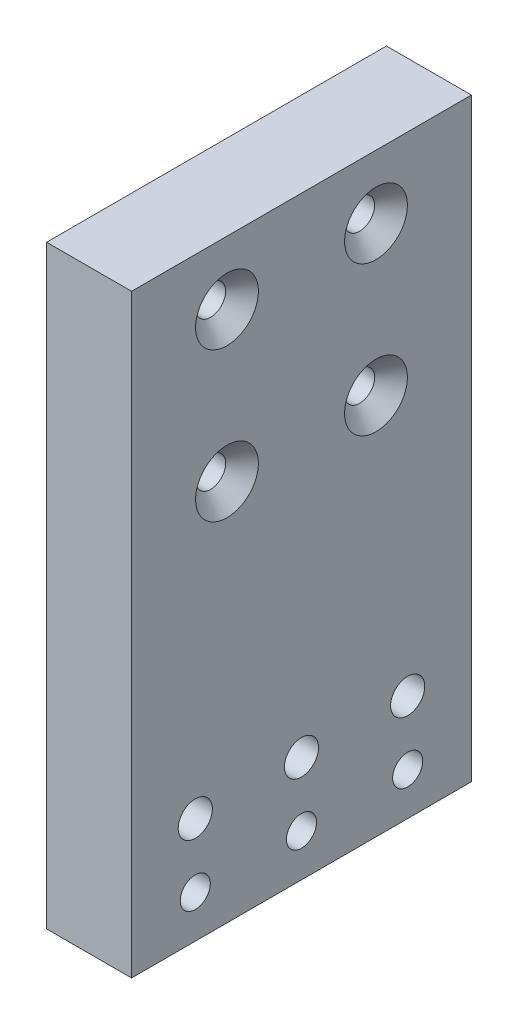
SolidWorks part; units mm, degrees
material "Nylon 6/10"
ref_plane "Front Plane" through (0, 0, 0) normal (0, 0, 1) x (1, 0, 0)
ref_plane "Top Plane" through (0, 0, 0) normal (0, 1, 0) x (1, 0, 0)
ref_plane "Right Plane" through (0, 0, 0) normal (1, 0, 0) x (0, 0, -1)
sketch "Sketch1" plane through (0, 0, 0) normal (1, 0, 0) x (0, 0, -1)
  line L1 (-25.4, -44.45) -> (25.4, -44.45)
  line L2 (-25.4, -44.45) -> (-25.4, 44.45)
  line L3 (-25.4, 44.45) -> (25.4, 44.45)
  line L4 (25.4, -44.45) -> (25.4, 44.45)
  line L5 (-25.4, -44.45) -> (25.4, 44.45) construction
  line L6 (-25.4, 44.45) -> (25.4, -44.45) construction
  point P0 (0, 0)
  dimension "D1" = 50.8
  dimension "D2" = 88.9
extrude "Boss-Extrude1" add sketch "Sketch1" along normal blind 12.7
hole_wizard "CSK for M4 Flat Head Machine Screw1" positions "Sketch3" profile "Sketch2" countersink size "M4" standard "ANSI Metric" end condition through all
sketch "Sketch3" plane through (12.7, 0, 0) normal (1, 0, 0) x (0, 0, -1)
  line L1 (-11.1369, 12.7) -> (11.1369, 12.7) construction
  line L2 (-11.1369, 12.7) -> (-11.1369, 34.9739) construction
  line L3 (-11.1369, 34.9739) -> (11.1369, 34.9739) construction
  line L4 (11.1369, 12.7) -> (11.1369, 34.9739) construction
  line L5 (-11.1369, 12.7) -> (11.1369, 34.9739) construction
  line L6 (-11.1369, 34.9739) -> (11.1369, 12.7) construction
  line L8 (25.4, 44.45) -> (-25.4, 44.45) construction
  point P219 (11.1369, 34.9739)
  point P223 (-11.1369, 34.9739)
  point P225 (-11.1369, 12.7)
  point P227 (11.1369, 12.7)
  dimension "D1" = 31.5
  dimension "D2" = 31.75
sketch "Sketch2" plane through (12.7, 34.9739, -11.1369) normal (0, 1, 0) x (0, 0, -1)
  line L0 (0, 0) -> (0, 12.7)
  line L1 (0, 12.7) -> (2.25, 12.7)
  line L2 (2.25, 12.7) -> (2.25, 2.45)
  line L3 (2.25, 2.45) -> (4.7, 0)
  line L5 (4.7, 0) -> (0, 0)
  line L6 (-2.25, 2.45) -> (-4.7, 0) construction
  line L11 (0, -6.35) -> (0, 107.95) construction
  dimension "Thru Hole Dia." = 4.5
  dimension "Thru Hole Depth" = 12.7
  dimension "Near C'Sink Dia." = 9.4
  dimension "Near C'Sink Angle" = 90
hole_wizard "CBORE for #10 Socket Head Cap Screw1" positions "Sketch5" profile "Sketch4" counterbore size "#10" standard "ANSI Inch" end condition through all
sketch "Sketch5" plane through (0, 0, 0) normal (-1, 0, 0) x (0, 0, 1)
  line L0 (-25.4, -28.575) -> (25.4, -28.575) construction
  line L1 (-25.4, -44.45) -> (-25.4, 44.45) construction
  line L2 (25.4, 44.45) -> (25.4, -44.45) construction
  line L4 (25.4, -44.45) -> (-25.4, -44.45) construction
  line L5 (0, -44.45) -> (0, 0) construction
  point P0 (-15.875, -28.575)
  point P2 (0, -28.575)
  point P4 (15.875, -28.575)
  dimension "D1" = 15.875
  dimension "D2" = 9.525
  dimension "D3" = 9.525
sketch "Sketch4" plane through (0, -28.575, -15.875) normal (0, 1, 0) x (0, 0, 1)
  line L0 (0, 0) -> (0, 12.7)
  line L1 (0, 12.7) -> (2.5527, 12.7)
  line L3 (2.5527, 12.7) -> (2.5527, 4.826)
  line L4 (2.5527, 4.826) -> (4.7625, 4.826)
  line L5 (4.7625, 4.826) -> (4.7625, 0)
  line L7 (4.7625, 0) -> (0, 0)
  line L11 (0, -6.35) -> (0, 107.95) construction
  dimension "Thru Hole Dia." = 5.1054
  dimension "Thru Hole Depth" = 12.7
  dimension "C'Bore Dia." = 9.525
  dimension "C'Bore Depth" = 4.826
hole_wizard "CBORE for #8 Socket Head Cap Screw1" positions "Sketch7" profile "Sketch6" counterbore size "#8" standard "ANSI Inch" end condition through all
sketch "Sketch7" plane through (0, 0, 0) normal (-1, 0, 0) x (0, 0, 1)
  line L0 (-25.4, -38.1) -> (25.4, -38.1) construction
  line L1 (-25.4, -44.45) -> (-25.4, 44.45) construction
  line L2 (25.4, 44.45) -> (25.4, -44.45) construction
  line L4 (25.4, -44.45) -> (-25.4, -44.45) construction
  point P0 (-15.875, -38.1)
  point P2 (0, -38.1)
  point P4 (15.875, -38.1)
  point P22 (16.7534, -38.7449)
  dimension "D1" = 15.875
  dimension "D2" = 15.875
  dimension "D3" = 6.35
sketch "Sketch6" plane through (0, -38.1, -15.875) normal (0, 1, 0) x (0, 0, 1)
  line L0 (0, 0) -> (0, 12.7)
  line L1 (0, 12.7) -> (2.2479, 12.7)
  line L3 (2.2479, 12.7) -> (2.2479, 4.1656)
  line L4 (2.2479, 4.1656) -> (3.9687, 4.1656)
  line L5 (3.9687, 4.1656) -> (3.9687, 0)
  line L7 (3.9687, 0) -> (0, 0)
  line L11 (0, -6.35) -> (0, 107.95) construction
  dimension "Thru Hole Dia." = 4.4958
  dimension "Thru Hole Depth" = 12.7
  dimension "C'Bore Dia." = 7.9375
  dimension "C'Bore Depth" = 4.1656
